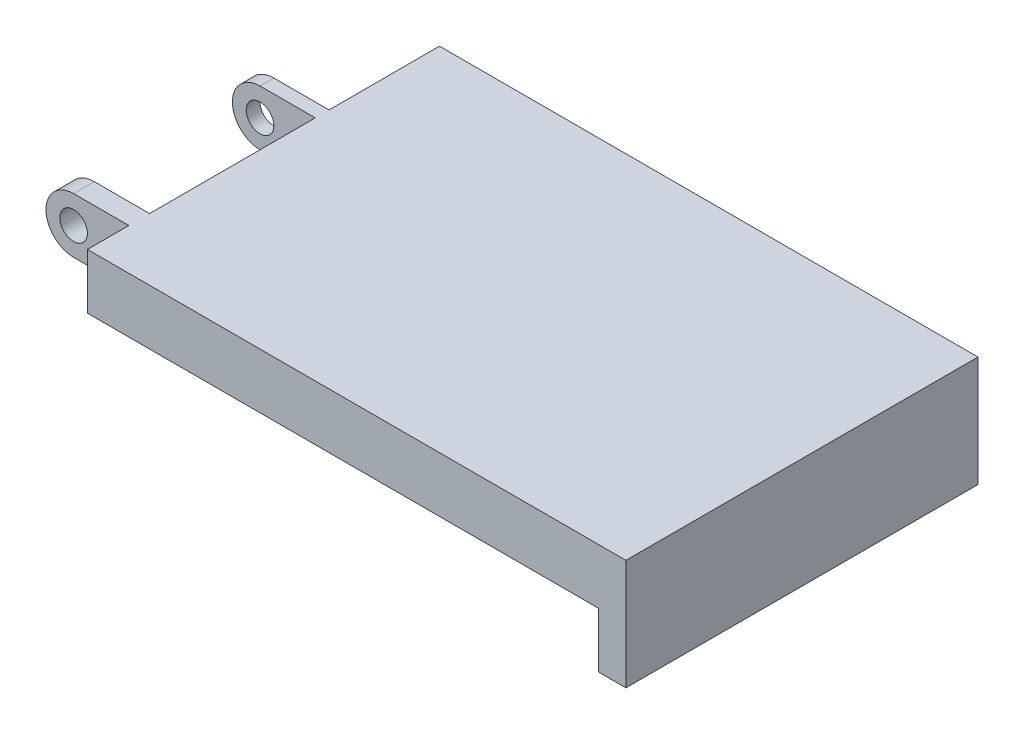
SolidWorks part; units mm, degrees
note: The reader was unsure of these and kept them because the rebuilt part matched: shared geometry of "草图3<2>".
ref_plane "前视基准面" through (0, 0, 0) normal (0, 0, 1) x (1, 0, 0)
ref_plane "上视基准面" through (0, 0, 0) normal (0, 1, 0) x (1, 0, 0)
ref_plane "右视基准面" through (0, 0, 0) normal (1, 0, 0) x (0, 0, -1)
sketch "草图1" plane through (0, 0, 0) normal (0, 0, 1) x (1, 0, 0)
  line L0 (0, 2) -> (43, 2)
  line L1 (43, 2) -> (43, -6)
  line L2 (43, -6) -> (41, -6)
  line L3 (41, -6) -> (41, -2)
  line L4 (41, -2) -> (0, -2)
  circle A0 centre (0, 0) radius 1
  arc A1 (0, 2) -> (0, -2) centre (0, 0) ccw
extrude "凸台-拉伸1" add sketch "草图1" along normal blind 25.5
sketch "草图2" plane through (0, 0, 25.5) normal (0, 0, 1) x (1, 0, 0)
  line L0 (4, -2) -> (4, 2)
  line L1 (43, 2) -> (0, 2) construction
  line L2 (4, 2) -> (-4, 2)
  line L3 (-4, 2) -> (-4, -2)
  line L4 (-4, -2) -> (4, -2)
extrude "切除-拉伸2" cut sketch "草图2" against normal blind 3
sketch "草图3" plane through (0, 0, 0) normal (0, 0, -1) x (-1, 0, 0)
  line L0 (0, 2) -> (-4, 2)
  line L1 (-43, 2) -> (0, 2) construction
  line L2 (-4, 2) -> (-4, -2)
  line L3 (0, -2) -> (-41, -2) construction
  line L4 (-4, -2) -> (0, -2)
  line L5 (0, 2) -> (-43, 2)
  line L6 (-43, 2) -> (-43, -6)
  line L7 (-43, -6) -> (-41, -6)
  line L8 (-41, -6) -> (-41, -2)
  line L9 (-41, -2) -> (0, -2)
  arc A1 (0, -2) -> (0, 2) centre (0, 0) ccw
  arc A2 (0, -2) -> (0, 2) centre (0, 0) ccw
  dimension "D1" = 0
extrude "切除-拉伸3" cut sketch "草图3" against normal blind 8
extrude "切除-拉伸4" cut sketch "草图3<2>" against normal blind 12 from offset 9 offset against normal yes
sketch "草图3<2>" plane through (0, 0, 0) normal (0, 0, -1) x (-1, 0, 0) same geometry as "草图3"
sketch "草图4" plane through (41, 0, 0) normal (-1, 0, 0) x (0, 0, 1)
  line L0 (13.75, -5.0684) -> (11.75, -5.0684)
  line L1 (25.5, -6) -> (0, -6) construction
  line L2 (12.75, -6) -> (13.75, -6)
  line L3 (13.75, -6) -> (13.75, -5.0684)
  line L4 (11.75, -5.0684) -> (11.75, -6)
  line L5 (11.75, -6) -> (12.75, -6)
extrude "凸台-拉伸2" add sketch "草图4" along normal blind 0.5
